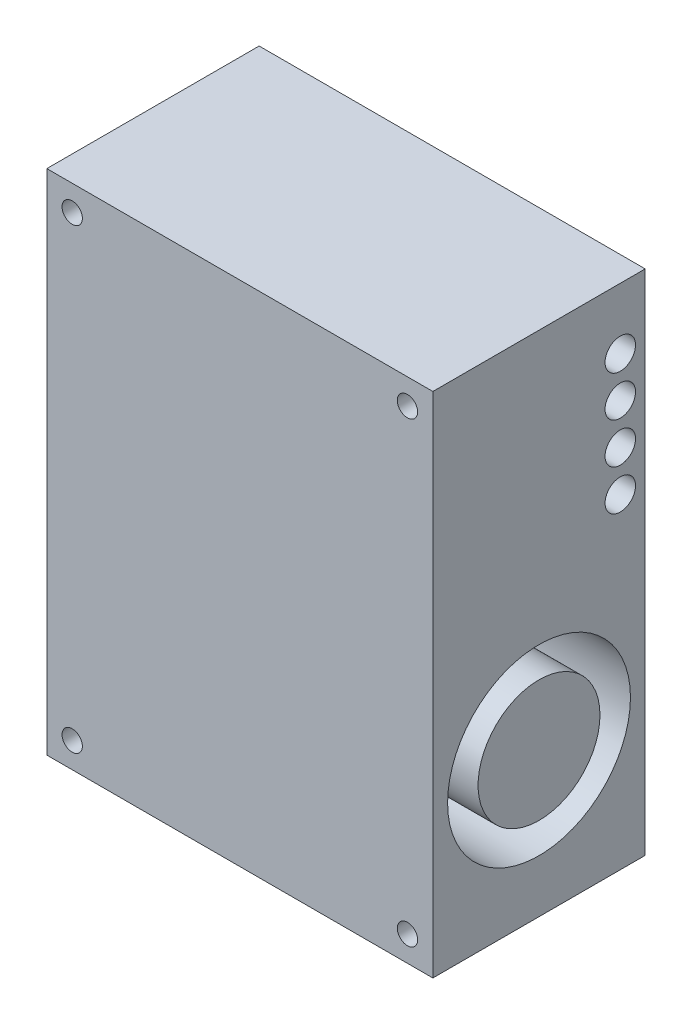
SolidWorks part; units mm, degrees
ref_plane "Front Plane" through (0, 0, 0) normal (0, 0, 1) x (1, 0, 0)
ref_plane "Top Plane" through (0, 0, 0) normal (0, 1, 0) x (1, 0, 0)
ref_plane "Right Plane" through (0, 0, 0) normal (1, 0, 0) x (0, 0, -1)
sketch "Sketch1" plane through (0, 0, 0) normal (0, 0, 1) x (1, 0, 0)
  line L1 (-19, 25) -> (19, 25)
  line L2 (-19, 25) -> (-19, -25)
  line L3 (-19, -25) -> (19, -25)
  line L4 (19, 25) -> (19, -25)
  dimension "D1" = 38
  dimension "D2" = 50
extrude "Boss-Extrude1" add sketch "Sketch1" along normal blind 20.9
sketch "Sketch2" plane through (-19, 0, 0) normal (-1, 0, 0) x (0, 0, 1)
  line L0 (0, 25) -> (0, -25) construction
  line L1 (12.4, -19.5) -> (7.5, -19.5)
  line L2 (12.4, -19.5) -> (12.4, -2.5)
  line L3 (12.4, -2.5) -> (7.5, -2.5)
  line L4 (7.5, -19.5) -> (7.5, -2.5)
  line L5 (20.9, -25) -> (0, -25) construction
  dimension "D1" = 17
  dimension "D2" = 4.9
  dimension "D3" = 7.5
  dimension "D4" = 5.5
extrude "Cut-Extrude1" cut sketch "Sketch2" against normal blind 10
sketch "Sketch3" plane through (19, 0, 0) normal (1, 0, 0) x (0, 0, -1)
  line L0 (-20.9, 25) -> (0, 25) construction
  line L1 (0, -25) -> (0, 25) construction
  circle A0 centre (-10.45, -10.8) radius 9
  circle A1 centre (-10.45, -10.8) radius 6
  circle A2 centre (-2.45, 19) radius 1.5
  circle A3 centre (-2.45, 15) radius 1.5
  circle A4 centre (-2.45, 11) radius 1.5
  circle A5 centre (-2.45, 7) radius 1.5
  point P4 (-10.45, 25)
  dimension "D2" = 18
  dimension "D3" = 12
  dimension "D8" = 3
  dimension "D1" = 35.8
  dimension "D4" = 6
  dimension "D5" = 2.45
  dimension "D7" = 12
  dimension "D6" = 4
extrude "Cut-Extrude2" cut sketch "Sketch3" against normal blind 10
sketch "Sketch7" plane through (0, 0, 20.9) normal (0, 0, 1) x (1, 0, 0)
  line L0 (19, 25) -> (-19, 25) construction
  line L1 (19, -25) -> (19, 25) construction
  circle A0 centre (16.5, 22.5) radius 1
  circle A1 centre (16.5, -22.5) radius 1
  circle A2 centre (-16.5, -22.5) radius 1
  circle A3 centre (-16.5, 22.5) radius 1
  point P4 (0, 25)
  point P7 (19, 0)
  dimension "D1" = 16.5
  dimension "D5" = 2
  dimension "D2" = 22.5
  dimension "D3" = 2
  dimension "D4" = 2
extrude "Cut-Extrude3" cut sketch "Sketch7" against normal blind 10
